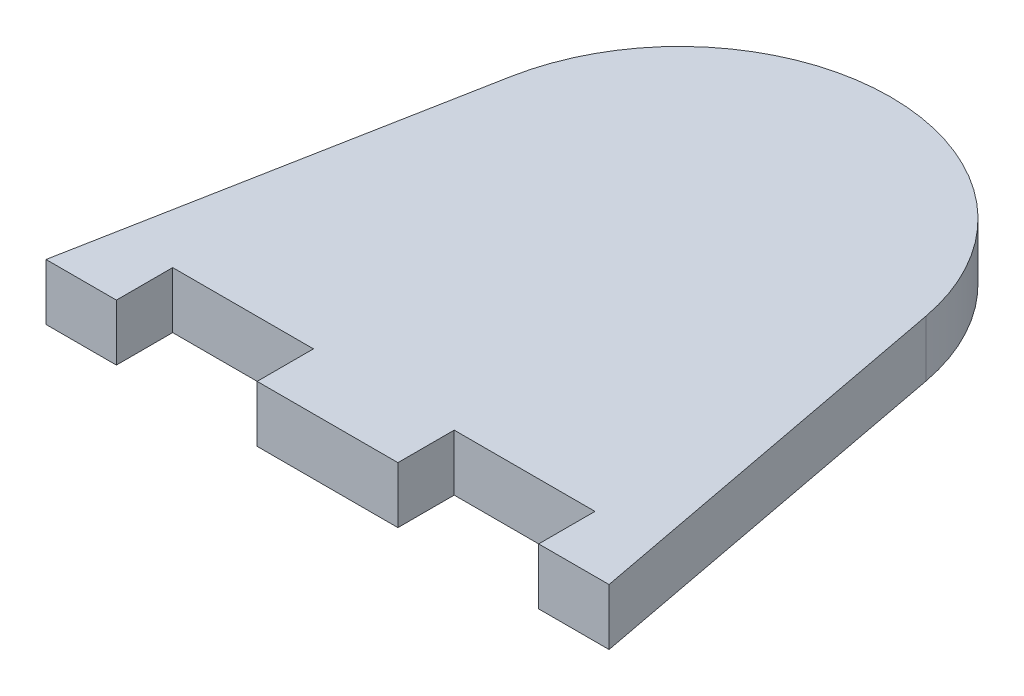
SolidWorks part; units mm, degrees
ref_plane "Front Plane" through (0, 0, 0) normal (0, 0, 1) x (1, 0, 0)
ref_plane "Top Plane" through (0, 0, 0) normal (0, 1, 0) x (1, 0, 0)
ref_plane "Right Plane" through (0, 0, 0) normal (1, 0, 0) x (0, 0, -1)
sketch "Sketch1" plane through (0, 0, 0) normal (0, 1, 0) x (1, 0, 0)
  line L0 (4.9528, -0.6851) -> (2.625, -17.5131)
  line L1 (-4.9528, -0.6851) -> (-2.625, -17.5131)
  line L2 (-20, -25) -> (20, -25)
  line L3 (20, -25) -> (14.7381, 2.7905)
  line L4 (-20, -25) -> (-14.7381, 2.7905)
  arc A0 (-2.625, -17.5131) -> (2.625, -17.5131) centre (0, -17.15) ccw
  arc A1 (4.9528, -0.6851) -> (-4.9528, -0.6851) centre (0, 0) ccw
  arc A2 (-3.015, -14.6939) -> (3.015, -14.6939) centre (0, 0) ccw
  arc A3 (14.7381, 2.7905) -> (-14.7381, 2.7905) centre (0, 0) ccw
  point P1 (0, 5)
  point P3 (0, -19.8)
  dimension "D1" = 5.3
  dimension "D2" = 10
  dimension "D4" = 30
  dimension "D3" = 24.8
  dimension "D5" = 20
  dimension "D6" = 20
  dimension "D7" = 25
extrude "Boss-Extrude1" add sketch "Sketch1" along normal blind 4 contours L3 A3 L4 L2 A1 L0 A0 L1 region at (-16.8133, 0, 11.21)
sketch "Sketch2" plane through (0, 4, 0) normal (0, 1, 0) x (1, 0, 0)
  line L0 (-4.9528, -0.6851) -> (-2.625, -17.5131)
  line L1 (2.625, -17.5131) -> (4.9528, -0.6851)
  arc A0 (4.9528, -0.6851) -> (-4.9528, -0.6851) centre (0, 0) ccw
  arc A1 (-2.625, -17.5131) -> (2.625, -17.5131) centre (0, -17.15) ccw
extrude "Boss-Extrude2" add sketch "Sketch2" against normal blind 2
sketch "Sketch3" plane through (0, 0, 0) normal (0, -1, 0) x (1, 0, 0)
  line L0 (-20, 25) -> (20, 25) construction
  line L1 (15, 25) -> (5, 25)
  line L2 (15, 25) -> (15, 21)
  line L3 (15, 21) -> (5, 21)
  line L4 (5, 25) -> (5, 21)
  line L6 (-5, 25) -> (-15, 25)
  line L7 (-5, 25) -> (-5, 21)
  line L8 (-5, 21) -> (-15, 21)
  line L9 (-15, 25) -> (-15, 21)
  dimension "D1" = 10
  dimension "D2" = 10
  dimension "D3" = 10
  dimension "D4" = 4
  dimension "D5" = 4
  dimension "D6" = 5
extrude "Cut-Extrude2" cut sketch "Sketch3" against normal blind 4
